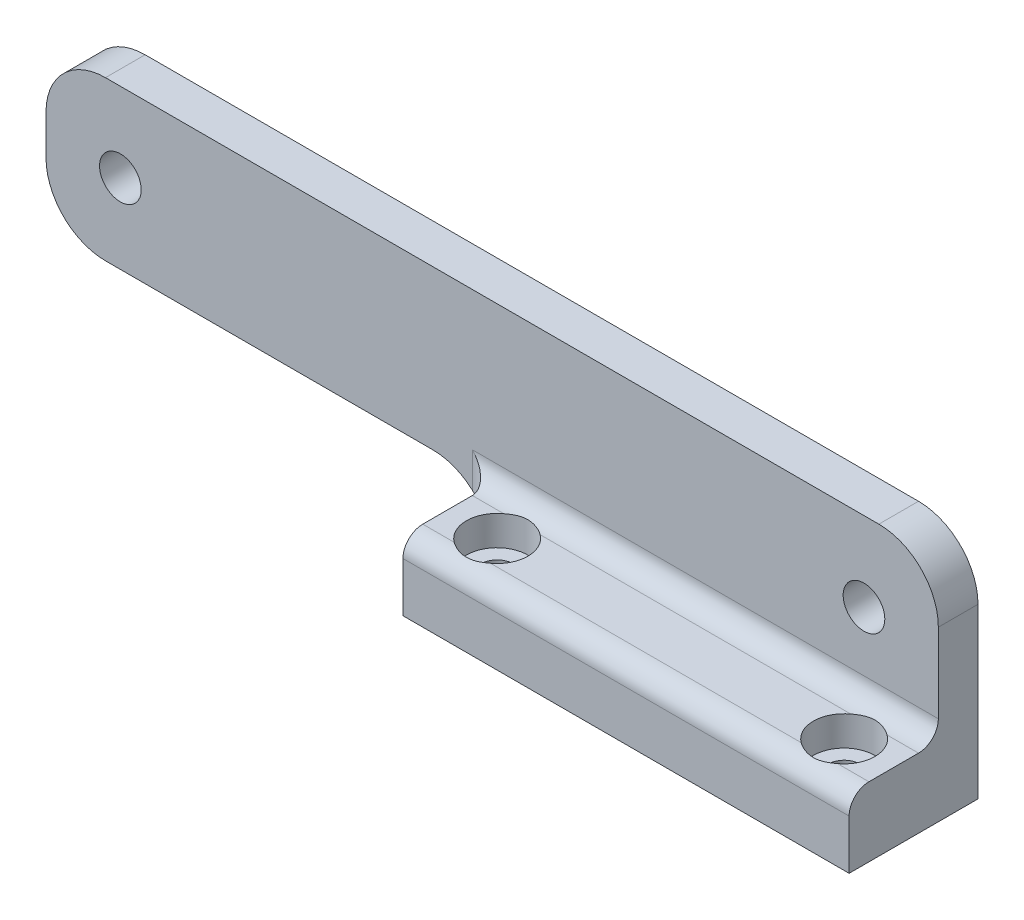
SolidWorks part; units mm, degrees
ref_plane "Plano frontal" through (0, 0, 0) normal (0, 0, 1) x (1, 0, 0)
ref_plane "Plano superior" through (0, 0, 0) normal (0, 1, 0) x (1, 0, 0)
ref_plane "Plano direito" through (0, 0, 0) normal (1, 0, 0) x (0, 0, -1)
sketch "Esboço1" plane through (0, 0, 0) normal (0, 0, 1) x (1, 0, 0)
  line L0 (-37.5, 0) -> (37.5, 0) construction
  line L1 (45, -8) -> (-45, -8)
  line L2 (45, -8) -> (45, 8)
  line L3 (45, 8) -> (-45, 8)
  line L4 (-45, -8) -> (-45, 8)
  line L5 (45, -8) -> (-45, 8) construction
  line L6 (45, 8) -> (-45, -8) construction
  circle A0 centre (-37.5, 0) radius 2.1
  circle A1 centre (37.5, 0) radius 2.1
  point P0 (0, 0)
  point P11 (-45, 0)
  point P12 (0, 0)
  dimension "D3" = 4.2
  dimension "D1" = 90
  dimension "D2" = 16
  dimension "D4" = 75
extrude "Ressalto-extrusão1" add sketch "Esboço1" along normal blind 4
sketch "Esboço2" plane through (0, -8, 0) normal (0, -1, 0) x (1, 0, 0)
  line L0 (-45, 4) -> (45, 4) construction
  line L5 (0, 0) -> (45, 0)
  line L6 (0, 0) -> (0, 13)
  line L7 (0, 13) -> (45, 13)
  line L8 (45, 0) -> (45, 13)
  line L9 (40, 8.5) -> (45, 8.5) construction
  line L10 (5, 8.5) -> (0, 8.5) construction
  circle A0 centre (40, 8.5) radius 1.6
  circle A1 centre (5, 8.5) radius 1.6
  dimension "D2" = 3.2
  dimension "D1" = 9
  dimension "D3" = 4.5
  dimension "D4" = 5
extrude "Ressalto-extrusão3" add sketch "Esboço2" along normal blind 7
fillet "Filete1" radius 6 4 edges at (45, 8, 2) (-45, 8, 2) (-45, -8, 2) (0, -8, 2)
fillet "Filete2" radius 2 2 edges at (22.5, -8, 4) (0, -11, 4)
sketch "Esboço3" plane through (0, -8, 0) normal (0, 1, 0) x (1, 0, 0)
  circle A0 centre (5, -8.5) radius 3.1
  circle A1 centre (40, -8.5) radius 3.1
  dimension "D1" = 6.2
extrude "Corte-extrusão1" cut sketch "Esboço3" against normal blind 3 and the other way blind 10
fillet "Filete3" radius 2 1 edges at (22.5, -8, 13)
